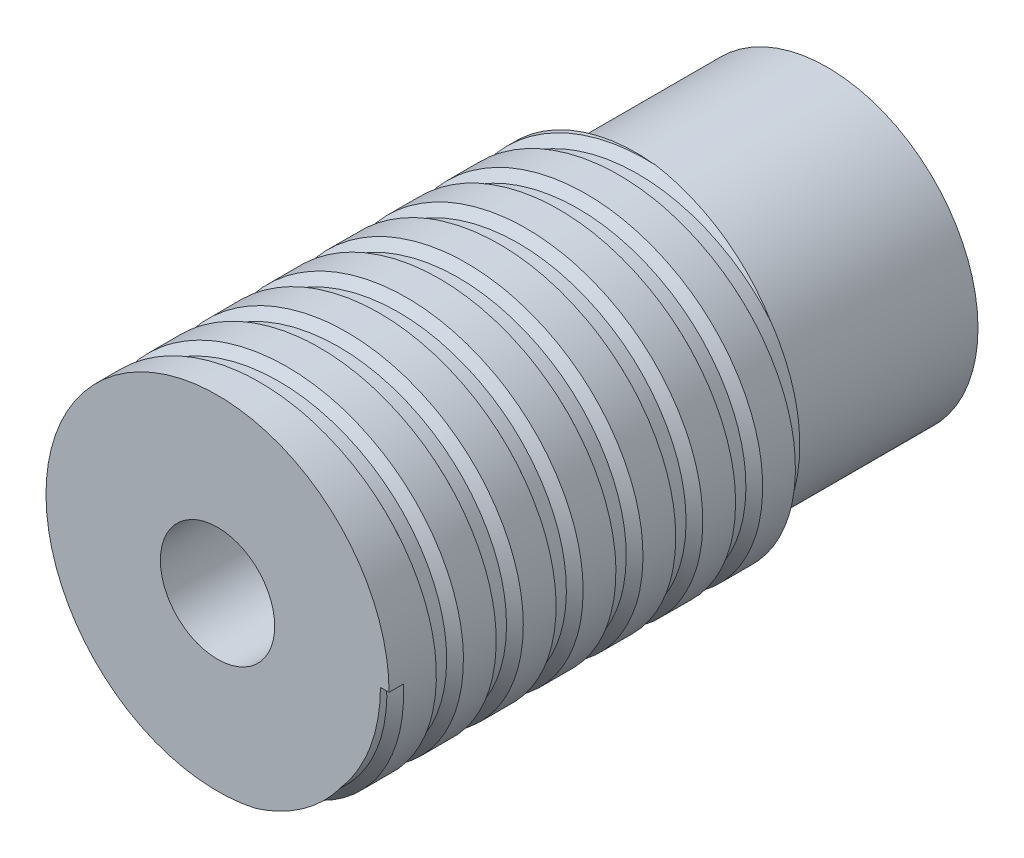
SolidWorks part; units mm, degrees
ref_plane "前视基准面" through (0, 0, 0) normal (0, 0, 1) x (1, 0, 0)
ref_plane "上视基准面" through (0, 0, 0) normal (0, 1, 0) x (1, 0, 0)
ref_plane "右视基准面" through (0, 0, 0) normal (1, 0, 0) x (0, 0, -1)
sketch "草图1" plane through (0, 0, 0) normal (0, 0, 1) x (1, 0, 0)
  circle A0 centre (0, 0) radius 7.9
  dimension "D1" = 15.8
extrude "凸台-拉伸1" add sketch "草图1" along normal blind 10
sketch "草图2" plane through (0, 0, 10) normal (0, 0, 1) x (1, 0, 0)
  circle A0 centre (0, 0) radius 9
  dimension "D1" = 18
extrude "凸台-拉伸2" add sketch "草图2" along normal blind 22
sketch "草图4" plane through (0, 0, 10) normal (0, 0, -1) x (-1, 0, 0)
  circle A0 centre (0, 0) radius 9
curve "螺旋线/涡状线1" pitch 3.14 height 21.98 turns 7
sketch "草图8" plane through (0, 0, 0) normal (0, 1, 0) x (1, 0, 0)
  line L0 (8.5477, -10.3743) -> (8.5477, -9.6987)
  line L1 (8.5477, -10.3743) -> (9, -10.6922)
  line L2 (9, -32) -> (9, -10) construction
  line L3 (9, -10.6922) -> (9, -9.2714)
  line L4 (9, -9.2714) -> (8.5477, -9.6987)
sweep "切除-扫描2" cut profiles "草图8" path "螺旋线/涡状线1"
sketch "草图9" plane through (0, 0, 0) normal (0, 0, -1) x (-1, 0, 0)
  circle A0 centre (0, 0) radius 3
  dimension "D1" = 6
extrude "切除-拉伸1" cut sketch "草图9" against normal up to next
